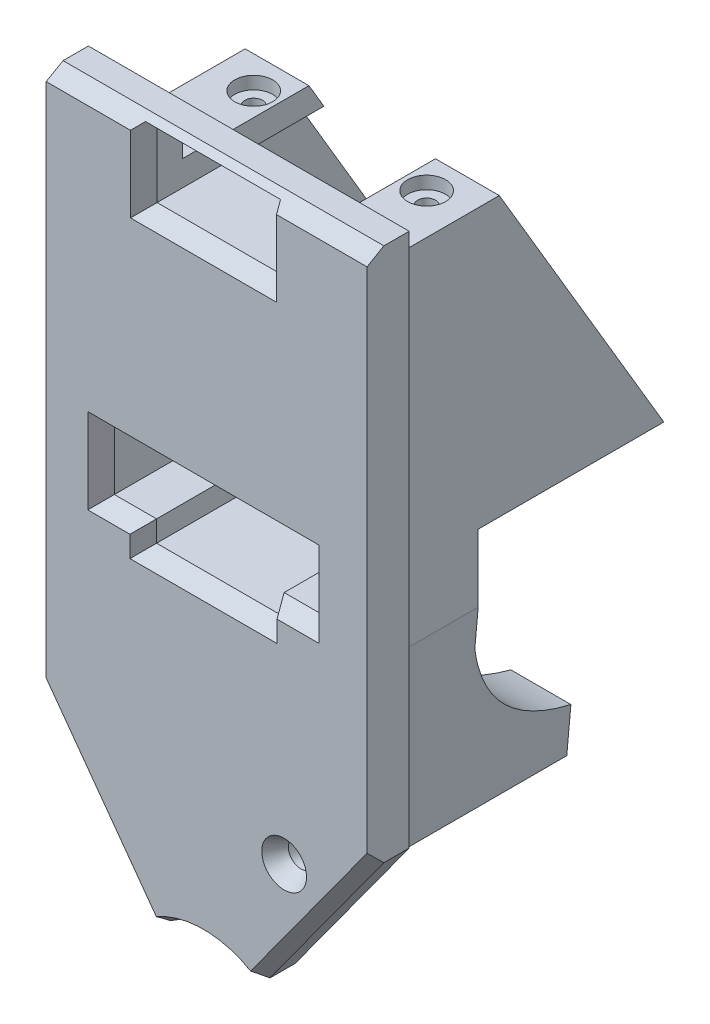
SolidWorks part; units mm, degrees
ref_plane "Front Plane" through (0, 0, 0) normal (0, 0, 1) x (1, 0, 0)
ref_plane "Top Plane" through (0, 0, 0) normal (0, 1, 0) x (1, 0, 0)
ref_plane "Right Plane" through (0, 0, 0) normal (1, 0, 0) x (0, 0, -1)
sketch "Sketch2" plane through (0, 0, 0) normal (0, 1, 0) x (1, 0, 0)
  line L0 (15.061, 0) -> (15.061, 32)
  line L1 (-12.561, 2.5) -> (12.561, 2.5)
  line L2 (-12.561, 2.5) -> (-12.561, 32)
  line L4 (12.561, 2.5) -> (12.561, 32)
  line L5 (15.061, 32) -> (12.561, 32)
  line L7 (-15.061, 32) -> (-15.061, 0)
  line L8 (-15.061, 0) -> (15.061, 0)
  line L10 (-15.061, 32) -> (-12.561, 32)
  point P4 (0, 2.5)
  point P12 (0, 0)
  dimension "D1" = 2.5
  dimension "D2" = 2.5
  dimension "D3" = 29.5
  dimension "D4" = 25.122
extrude "Boss-Extrude1" add sketch "Sketch2" along normal blind 32.5
sketch "Sketch4" plane through (0, 0, 0) normal (0, -1, 0) x (1, 0, 0)
  line L10 (-7.561, -6) -> (-7.561, 0)
  line L13 (-12.561, -2.5) -> (-12.561, -32) construction
  line L18 (-12.561, -10) -> (-7.561, -6)
  line L23 (12.561, -32) -> (12.561, -2.5) construction
  line L26 (12.561, -10) -> (7.561, -6)
  line L33 (-15.061, -32) -> (-15.061, 0) construction
  line L36 (15.061, 0) -> (15.061, -32) construction
  line L38 (-7.561, 0) -> (-15.061, 0)
  line L39 (7.561, -6) -> (7.561, 0)
  line L40 (7.561, 0) -> (15.061, 0)
  line L41 (-15.061, 0) -> (-15.061, -32)
  line L42 (-15.061, -32) -> (-12.561, -32)
  line L43 (-12.561, -32) -> (-15.061, -32) construction
  line L44 (-12.561, -32) -> (-12.561, -10)
  line L45 (12.561, -10) -> (12.561, -32)
  line L46 (12.561, -32) -> (15.061, -32)
  line L47 (15.061, -32) -> (15.061, 0)
  circle A2 centre (-10.2499, -4.95) radius 1.05
  circle A5 centre (10.2499, -4.95) radius 1.05
  dimension "D4" = 6
  dimension "D5" = 2.1
  dimension "D1" = 7.5
  dimension "D2" = 7.5
  dimension "D3" = 10
extrude "Boss-Extrude2" add sketch "Sketch4" along normal blind 2.5
sketch "Sketch5" plane through (0, 32.5, 0) normal (0, 1, 0) x (1, 0, 0)
  line L0 (-15.061, 32) -> (-10.2499, 32)
  line L9 (-10.2499, 32) -> (-6.25, 26)
  line L13 (-15.061, 0) -> (15.061, 0) construction
  line L14 (15.061, 0) -> (-15.061, 0)
  line L15 (-15.061, 0) -> (-15.061, 32)
  line L20 (15.061, 0) -> (15.061, 32)
  line L21 (-6.25, 26) -> (6.25, 26)
  line L22 (6.25, 26) -> (10.2499, 32)
  line L23 (10.2499, 32) -> (15.061, 32)
  circle A0 centre (-10.2499, 4.95) radius 1.05 construction
  circle A1 centre (-10.2499, 8.7) radius 1.05
  circle A2 centre (10.2499, 8.7) radius 1.05
  point P6 (0, 26)
  dimension "D4" = 0
  dimension "D1" = 8.7
  dimension "D2" = 12.5
  dimension "D3" = 20.4998
  dimension "D5" = 6
extrude "Boss-Extrude3" add sketch "Sketch5" along normal blind 3
sketch "Sketch6" plane through (-15.061, 0, 0) normal (-1, 0, 0) x (0, 0, 1)
  line L0 (-12.5, 35.5) -> (-32, 2.5)
  line L1 (-32, 2.5) -> (-32, 35.5)
  line L2 (-32, 35.5) -> (-12.5, 35.5)
  line L3 (-32, 35.5) -> (-32, -2.5) construction
  line L4 (-32, 35.5) -> (0, 35.5) construction
  line L6 (0, -2.5) -> (-32, -2.5) construction
  line L7 (0, 35.5) -> (0, -2.5) construction
  dimension "D1" = 5
  dimension "D2" = 12.5
extrude "Cut-Extrude1" cut sketch "Sketch6" against normal through all
ref_plane "Plane1" through (0, 16.5, 0) normal (0, -1, 0) x (-1, 0, 0)
sketch "Sketch13" plane through (0, 0, 0) normal (0, 0, 1) x (1, 0, 0)
  line L1 (-15.061, 35.5) -> (15.061, 35.5)
  line L2 (-15.061, 35.5) -> (-15.061, -2.5)
  line L3 (-15.061, -2.5) -> (15.061, -2.5)
  line L4 (15.061, 35.5) -> (15.061, -2.5)
extrude "Boss-Extrude7" add sketch "Sketch13" along normal blind 2.5
sketch "Sketch8" plane through (0, 0, 2.5) normal (0, 0, 1) x (1, 0, 0)
  line L0 (0, -48.5) -> (-47.2253, 16.5)
  line L1 (-16.5671, 16.5) -> (16.5671, 16.5) construction
  line L2 (-47.2253, 16.5) -> (47.2253, 16.5)
  line L3 (47.2253, 16.5) -> (0, -48.5)
  dimension "D1" = 72
  dimension "D2" = 65
extrude "Boss-Extrude4" add sketch "Sketch8" along normal blind 5
sketch "Sketch9" plane through (0, 0, 2.5) normal (0, 0, 1) x (1, 0, 0)
  line L0 (47.2253, 16.5) -> (65.3888, 41.5)
  line L1 (65.3888, 41.5) -> (-65.3888, 41.5)
  line L2 (-65.3888, 41.5) -> (-47.2253, 16.5)
  line L3 (47.2253, 16.5) -> (-47.2253, 16.5)
  line L4 (0, -48.5) -> (47.2253, 16.5) construction
  line L5 (-47.2253, 16.5) -> (0, -48.5) construction
  dimension "D1" = 25
extrude "Boss-Extrude6" add sketch "Sketch9" along normal up to surface (5 mm away) up to face at (0, -5.1667, 7.5)
sketch "Sketch10" plane through (0, 0, 2.5) normal (0, 0, -1) x (-1, 0, 0)
  line L1 (65.3888, 41.5) -> (32.6888, 41.5)
  line L2 (-65.3888, 41.5) -> (65.3888, 41.5) construction
  line L13 (32.6888, 41.5) -> (54.0913, 25.9502)
  line L15 (65.3888, 41.5) -> (0, -48.5) construction
  line L17 (54.0913, 25.9502) -> (65.3888, 41.5)
  line L19 (-65.3888, 41.5) -> (-32.6888, 41.5)
  line L23 (-32.6888, 41.5) -> (-54.0913, 25.9502)
  line L34 (0, -48.5) -> (-65.3888, 41.5) construction
  line L35 (-54.0913, 25.9502) -> (-65.3888, 41.5)
  dimension "D1" = 36
  dimension "D2" = 36
  dimension "D3" = 32.7
  dimension "D4" = 32.7
extrude "Cut-Extrude2" cut sketch "Sketch10" against normal through all
sketch "Sketch14" plane through (0, 0, -2.5) normal (0, 0, -1) x (-1, 0, 0)
  line L11 (-7.561, -2.5) -> (7.561, -2.5)
  line L12 (15.061, -2.5) -> (-15.061, -2.5) construction
  line L13 (7.561, -2.5) -> (7.561, 0)
  line L14 (12.561, 0) -> (7.561, 0) construction
  line L15 (7.561, -2.5) -> (7.561, 0) construction
  line L16 (7.561, 0) -> (12.561, 0)
  line L17 (12.561, 0) -> (12.561, 7.7837)
  line L18 (12.561, 2.5) -> (12.561, 32.5) construction
  line L19 (12.561, 7.7837) -> (-12.561, 7.7837)
  line L20 (-12.561, 32.5) -> (-12.561, 2.5) construction
  line L21 (-12.561, 7.7837) -> (-12.561, 0)
  line L22 (-12.561, 2.5) -> (-12.561, -2.5) construction
  line L23 (-7.561, 0) -> (-12.561, 0) construction
  line L24 (-12.561, 0) -> (-7.561, 0)
  line L25 (-7.561, 0) -> (-7.561, -2.5)
  line L26 (-7.561, -2.5) -> (-12.561, -2.5) construction
  line L27 (-15.061, 35.5) -> (15.061, 35.5) construction
  line L28 (-7.5, 35.5) -> (7.5, 35.5)
  line L29 (-7.5, 35.5) -> (-7.5, 40.5)
  line L30 (-7.5, 40.5) -> (7.5, 40.5)
  line L31 (7.5, 35.5) -> (7.5, 40.5)
  point P37 (0, 35.5)
  dimension "D1" = 15
  dimension "D2" = 5
extrude "Cut-Extrude3" cut sketch "Sketch14" against normal through all
sketch "Sketch15" plane through (0, -2.5, 0) normal (0, -1, 0) x (1, 0, 0)
  line L1 (15.061, -32) -> (-15.061, -32)
  line L2 (15.061, -32) -> (15.061, 2.5)
  line L3 (15.061, 2.5) -> (-15.061, 2.5)
  line L4 (-15.061, -32) -> (-15.061, 2.5)
  circle A0 centre (-10.2499, -4.95) radius 2.495
  circle A1 centre (10.341, -4.95) radius 2.495
  dimension "D1" = 4.99
  dimension "D2" = 4.99
extrude "Boss-Extrude8" add sketch "Sketch15" along normal blind 3
sketch "Sketch17" plane through (0, -5.5, 0) normal (0, -1, 0) x (1, 0, 0)
  line L0 (15.061, 2.5) -> (-15.061, 2.5) construction
  circle A0 centre (0, -37.5) radius 13.75
  dimension "D2" = 27.5
  dimension "D1" = 40
extrude "Cut-Extrude4" cut sketch "Sketch17" against normal through all
sketch "Sketch19" plane through (0, 0, -2.5) normal (0, 0, -1) x (-1, 0, 0)
  line L0 (-15.061, 35.5) -> (15.061, 35.5) construction
  line L1 (7.5, 35.5) -> (-7.5, 35.5)
  line L2 (7.5, 35.5) -> (7.5, 32.5)
  line L3 (7.5, 32.5) -> (-7.5, 32.5)
  line L4 (-7.5, 35.5) -> (-7.5, 32.5)
  line L5 (7.5, 35.5) -> (7.5, 40.5) construction
  line L6 (-7.5, 40.5) -> (-7.5, 35.5) construction
  line L7 (-12.561, 32.5) -> (12.561, 32.5) construction
  dimension "D1" = 0
  dimension "D2" = 0
  dimension "D3" = 0
extrude "Cut-Extrude6" cut sketch "Sketch19" along normal through all both and the other way through all
sketch "Sketch21" plane through (0, 35.5, 0) normal (0, 1, 0) x (1, 0, 0)
  circle A0 centre (-10.2499, 8.7) radius 2.25
  circle A1 centre (10.2499, 8.7) radius 2.25
  dimension "D1" = 4.5
  dimension "D2" = 4.5
extrude "Cut-Extrude8" cut sketch "Sketch21" against normal blind 1.5
ref_axis "Axis1" through (0, -48.5, 11.5724) along (0, 0, -1)
sketch "Sketch20" plane through (0, 0, 2.5) normal (0, 0, -1) x (-1, 0, 0)
  circle A0 centre (0, -48.5) radius 10
  dimension "D1" = 20
extrude "Here" cut sketch "Sketch20" against normal through all
sketch "Sketch22" plane through (0, 0, 2.5) normal (0, 0, -1) x (-1, 0, 0)
  line L3 (-13.061, -28) -> (-6.061, -28)
  line L5 (-15.061, -5.5) -> (-13.061, -28)
  line L6 (-15.061, -5.5) -> (0, -5.5)
  line L7 (-12.6021, -5.5) -> (12.6021, -5.5) construction
  circle A0 centre (-9.561, -25.875) radius 1.5
  spline S0 degree 2 poles (-6.061, -28) (-7.9807, -15.4199) (0, -5.5) knots 0 0 0 1 1 1
  point P9 (-9.561, -28)
  dimension "D4" = 3
  dimension "D1" = 22.5
  dimension "D2" = 2
  dimension "D3" = 7
  dimension "D5" = 2.125
  dimension "D6" = 0
extrude "Boss-Extrude9" add sketch "Sketch22" along normal blind 25
sketch "Sketch23" plane through (0, 0, -22.5) normal (0, 0, -1) x (-1, 0, 0)
  circle A0 centre (-9.561, -25.875) radius 1.5
  circle A1 centre (-9.561, -25.875) radius 1.5 construction
extrude "Cut-Extrude9" cut sketch "Sketch23" against normal through all
sketch "Sketch25" plane through (15.061, 0, 0) normal (1, 0, 0) x (0, 0, -1)
  line L1 (10, -5.5) -> (10, -10)
  line L2 (22.5, -5.5) -> (22.5, -28) construction
  line L3 (22.5, -22.5) -> (22.5, -5.5)
  line L6 (22.5, -5.5) -> (10, -5.5)
  line L7 (22.5, -5.5) -> (-2.5, -5.5) construction
  spline S0 degree 2 poles (22.5, -22.5) (12.0954, -19.9114) (10, -10) knots 0 0 0 1 1 1
  point P3 (12.8373, -16.75)
  point P11 (10, -5.5)
  dimension "D1" = 12.5
  dimension "D2" = 17
  dimension "D3" = 4.5
  dimension "D4" = 3
  dimension "D5" = 6.75
extrude "Cut-Extrude10" cut sketch "Sketch25" against normal through all
sketch "Sketch27" plane through (0, -28, 0) normal (0, -1, 0) x (1, 0, 0)
  circle A0 centre (10.341, -4.95) radius 2.495
  circle A1 centre (10.341, -4.95) radius 2.495 construction
  dimension "D1" = 0
extrude "Cut-Extrude12" cut sketch "Sketch27" against normal blind 22.5
sketch "Sketch28" plane through (0, -5.5, 0) normal (0, -1, 0) x (1, 0, 0)
  line L0 (-8.6832, -26.8387) -> (15.061, -10)
  line L1 (15.061, -10) -> (15.061, -37.5)
  line L2 (15.061, -37.5) -> (-8.6832, -26.8387)
  arc A0 (12.6021, -32) -> (-12.6021, -32) centre (0, -37.5) ccw construction
extrude "Cut-Extrude13" cut sketch "Sketch28" against normal up to vertex (8 mm away) up to point (15.061, 2.5, -32)
chamfer "Chamfer1" distance 2 angle 30 19 edges at (-29.9846, -7.2298, 7.5) (0, 41.5, 7.5) (29.9846, -7.2298, 7.5) (7.5, 36.5, 7.5) (0, 40.5, 7.5) (-7.5, 36.5, 7.5) (0, 32.5, 7.5) (12.561, 3.8918, 7.5) (0, 7.7837, 7.5) (-12.561, 3.8918, 7.5) (-10.061, 0, 7.5) (-7.561, -1.25, 7.5) (0, -2.5, 7.5) (7.561, -1.25, 7.5) (10.061, 0, 7.5) (0, -38.5, 7.5) (-43.39, 33.7251, 7.5) (43.39, 33.7251, 7.5) (8.061, -25.875, 7.5) first distance on face at (-29.9846, -7.2298, 5) first distance on face at (0, 41.5, 5) first distance on face at (29.9846, -7.2298, 5) first distance on face at (7.5, 35.6429, -1.3247) first distance on face at (0, 40.5, 5) first distance on face at (-7.5, 35.6429, -1.3247) first distance on face at (0, 32.5, 2.5) first distance on face at (12.561, 7.5659, -10.1484) first distance on face at (0, 7.7837, 2.5) first distance on face at (-12.561, 8.6917, -9.7874) first distance on face at (-10.061, 0, -0.25) first distance on face at (-7.561, -1.25, 0.75) first distance on face at (-0.8504, -2.5, -9.5613) first distance on face at (7.561, -1.25, 0.75) first distance on face at (10.061, 0, -0.25) first distance on face at (0, -39.4549, 5) first distance on face at (-43.39, 33.7251, 5) first distance on face at (43.39, 33.7251, 5) first distance on face at (8.0651, -25.9858, -3.9276)
sketch "Sketch29" plane through (0, 0, 2.5) normal (0, 0, -1) x (-1, 0, 0)
  line L1 (-19.3826, 46.14) -> (-58.2712, 46.14)
  line L2 (-19.3826, 46.14) -> (-19.3826, -41.2668)
  line L3 (-19.3826, -41.2668) -> (-58.2712, -41.2668)
  line L4 (-58.2712, 46.14) -> (-58.2712, -41.2668)
  line L5 (18.6419, 46.14) -> (60.6169, 46.14)
  line L6 (18.6419, 46.14) -> (18.6419, -41.2668)
  line L7 (18.6419, -41.2668) -> (60.6169, -41.2668)
  line L8 (60.6169, 46.14) -> (60.6169, -41.2668)
extrude "Test_Print" cut sketch "Sketch29" against normal through all both and the other way through all
